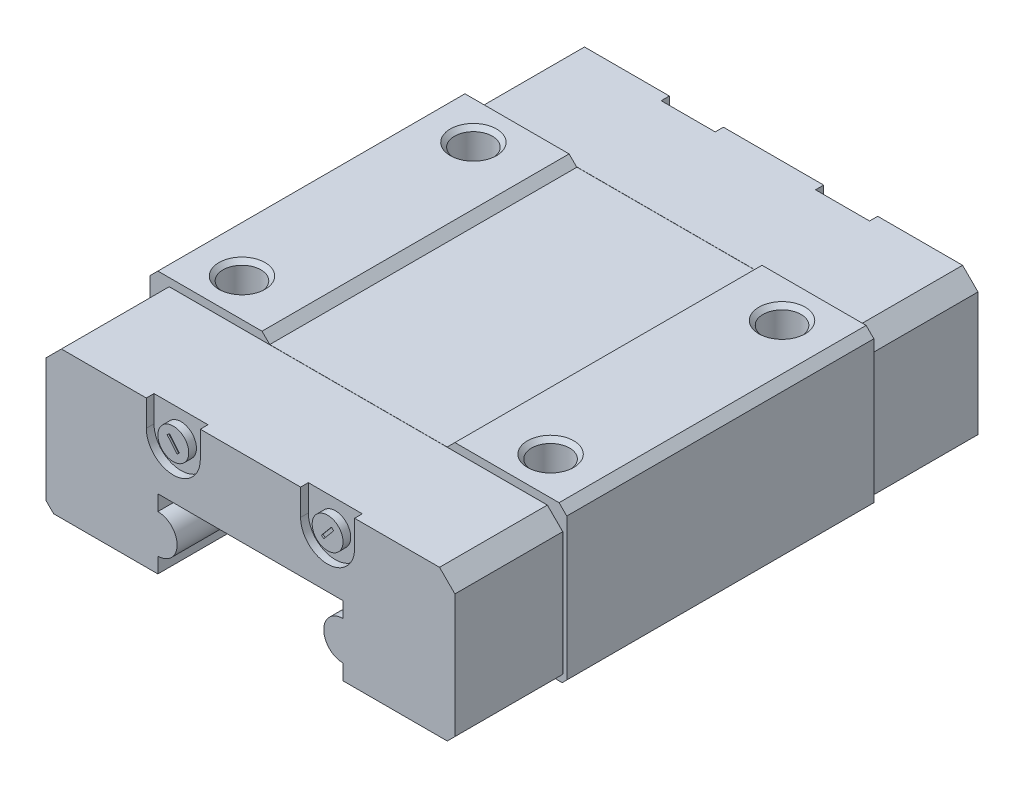
SolidWorks part; units mm, degrees
ref_plane "前视基准面" through (0, 0, 0) normal (0, 0, 1) x (1, 0, 0)
ref_plane "上视基准面" through (0, 0, 0) normal (0, 1, 0) x (1, 0, 0)
ref_plane "右视基准面" through (0, 0, 0) normal (1, 0, 0) x (0, 0, -1)
sketch "草图1" plane through (0, 0, 0) normal (0, 0, 1) x (1, 0, 0)
  line L0 (-13.5, 9.5) -> (-13.5, 0.297)
  line L1 (-13.5, 0.297) -> (-13.203, 0)
  line L2 (-13.203, 0) -> (-6, 0)
  line L3 (-6, 0) -> (-6, 1)
  line L4 (-6, 3.5) -> (-6, 4.5)
  line L5 (-6, 4.5) -> (6, 4.5)
  line L6 (6, 4.5) -> (6, 3.5)
  line L7 (6, 1) -> (6, 0)
  line L8 (6, 0) -> (13.203, 0)
  line L9 (13.203, 0) -> (13.5, 0.297)
  line L10 (13.5, 0.297) -> (13.5, 9.5)
  line L11 (13.5, 9.5) -> (13, 10)
  line L12 (13, 10) -> (6.25, 10)
  line L13 (6.25, 10) -> (5.75, 9.5)
  line L14 (5.75, 9.5) -> (-5.75, 9.5)
  line L15 (-5.75, 9.5) -> (-6.25, 10)
  line L16 (-6.25, 10) -> (-13, 10)
  line L17 (-13, 10) -> (-13.5, 9.5)
  arc A0 (-6, 1) -> (-6, 3.5) centre (-6, 2.25) ccw
  arc A1 (6, 3.5) -> (6, 1) centre (6, 2.25) ccw
extrude "凸台-拉伸1" add sketch "草图1" against normal blind 9.95 and the other way blind 9.95
ref_plane "基准面4" through (0, 0, 9.95) normal (0, 0, 1) x (1, 0, 0)
ref_plane "基准面5" through (0, 0, -9.95) normal (0, 0, 1) x (1, 0, 0)
sketch "草图2" plane through (0, 0, 9.95) normal (0, 0, 1) x (1, 0, 0)
  line L0 (-13.25, 8.503) -> (-13.25, 0.495)
  line L1 (-13.25, 0.495) -> (-12.755, 0)
  line L2 (-12.755, 0) -> (-6, 0)
  line L3 (-6, 0) -> (-6, 1)
  line L4 (-6, 3.5) -> (-6, 4.5)
  line L5 (-6, 4.5) -> (6, 4.5)
  line L6 (6, 4.5) -> (6, 3.5)
  line L7 (6, 1) -> (6, 0)
  line L8 (6, 0) -> (12.755, 0)
  line L9 (12.755, 0) -> (13.25, 0.495)
  line L10 (13.25, 0.495) -> (13.25, 8.503)
  line L11 (13.25, 8.503) -> (12.253, 9.5)
  line L12 (12.253, 9.5) -> (-12.253, 9.5)
  line L13 (-12.253, 9.5) -> (-13.25, 8.503)
  arc A0 (-6, 1) -> (-6, 3.5) centre (-6, 2.25) ccw
  arc A1 (6, 3.5) -> (6, 1) centre (6, 2.25) ccw
extrude "凸台-拉伸2" add sketch "草图2" along normal blind 7
sketch "草图3" plane through (0, 0, 9.95) normal (0, 0, 1) x (1, 0, 0)
  line L0 (-33.9, 33.9) -> (-33.9, -33.9)
  line L1 (-33.9, -33.9) -> (33.9, -33.9)
  line L2 (33.9, -33.9) -> (33.9, 33.9)
  line L3 (33.9, 33.9) -> (-33.9, 33.9)
  line L4 (-13.24, 8.493) -> (-13.24, 0.505)
  line L5 (-13.24, 0.505) -> (-12.745, 0.01)
  line L6 (-12.745, 0.01) -> (-6.01, 0.01)
  line L7 (-6.01, 0.01) -> (-6.01, 1.03)
  line L8 (-6.01, 3.49) -> (-6.01, 4.52)
  line L9 (-6.01, 4.52) -> (6.01, 4.52)
  line L10 (6.01, 4.52) -> (6.01, 3.49)
  line L11 (6.01, 1.03) -> (6.01, 0.01)
  line L12 (6.01, 0.01) -> (12.745, 0.01)
  line L13 (12.745, 0.01) -> (13.24, 0.505)
  line L14 (13.24, 0.505) -> (13.24, 8.493)
  line L15 (13.24, 8.493) -> (12.243, 9.49)
  line L16 (12.243, 9.49) -> (-12.243, 9.49)
  line L17 (-12.243, 9.49) -> (-13.24, 8.493)
  arc A0 (-6.01, 1.03) -> (-6.01, 3.49) centre (-6.01, 2.26) ccw
  arc A1 (6.01, 3.49) -> (6.01, 1.03) centre (6.01, 2.26) ccw
extrude "切除-拉伸1" cut sketch "草图3" along normal blind 0.02
sketch "草图4" plane through (0, 0, -9.95) normal (0, 0, 1) x (1, 0, 0)
  line L0 (-13.25, 8.503) -> (-13.25, 0.495)
  line L1 (-13.25, 0.495) -> (-12.755, 0)
  line L2 (-12.755, 0) -> (-6, 0)
  line L3 (-6, 0) -> (-6, 1)
  line L4 (-6, 3.5) -> (-6, 4.5)
  line L5 (-6, 4.5) -> (6, 4.5)
  line L6 (6, 4.5) -> (6, 3.5)
  line L7 (6, 1) -> (6, 0)
  line L8 (6, 0) -> (12.755, 0)
  line L9 (12.755, 0) -> (13.25, 0.495)
  line L10 (13.25, 0.495) -> (13.25, 8.503)
  line L11 (13.25, 8.503) -> (12.253, 9.5)
  line L12 (12.253, 9.5) -> (-12.253, 9.5)
  line L13 (-12.253, 9.5) -> (-13.25, 8.503)
  arc A0 (-6, 1) -> (-6, 3.5) centre (-6, 2.25) ccw
  arc A1 (6, 3.5) -> (6, 1) centre (6, 2.25) ccw
extrude "凸台-拉伸3" add sketch "草图4" against normal blind 7
sketch "草图5" plane through (0, 0, -9.95) normal (0, 0, 1) x (1, 0, 0)
  line L0 (-33.9, 33.9) -> (-33.9, -33.9)
  line L1 (-33.9, -33.9) -> (33.9, -33.9)
  line L2 (33.9, -33.9) -> (33.9, 33.9)
  line L3 (33.9, 33.9) -> (-33.9, 33.9)
  line L4 (-13.24, 8.493) -> (-13.24, 0.505)
  line L5 (-13.24, 0.505) -> (-12.745, 0.01)
  line L6 (-12.745, 0.01) -> (-6.01, 0.01)
  line L7 (-6.01, 0.01) -> (-6.01, 1.03)
  line L8 (-6.01, 3.49) -> (-6.01, 4.52)
  line L9 (-6.01, 4.52) -> (6.01, 4.52)
  line L10 (6.01, 4.52) -> (6.01, 3.49)
  line L11 (6.01, 1.03) -> (6.01, 0.01)
  line L12 (6.01, 0.01) -> (12.745, 0.01)
  line L13 (12.745, 0.01) -> (13.24, 0.505)
  line L14 (13.24, 0.505) -> (13.24, 8.493)
  line L15 (13.24, 8.493) -> (12.243, 9.49)
  line L16 (12.243, 9.49) -> (-12.243, 9.49)
  line L17 (-12.243, 9.49) -> (-13.24, 8.493)
  arc A0 (-6.01, 1.03) -> (-6.01, 3.49) centre (-6.01, 2.26) ccw
  arc A1 (6.01, 3.49) -> (6.01, 1.03) centre (6.01, 2.26) ccw
extrude "切除-拉伸2" cut sketch "草图5" against normal blind 0.02
ref_plane "基准面6" through (0, 0, -16.95) normal (0, 0, 1) x (1, 0, 0)
sketch "草图6" plane through (0, 0, -16.95) normal (0, 0, 1) x (1, 0, 0)
  line L0 (-6.75, 26) -> (-6.75, 7.8)
  line L1 (-3.25, 7.8) -> (-3.25, 24.825)
  line L2 (-3.25, 24.825) -> (3.25, 24.825)
  line L3 (3.25, 24.825) -> (3.25, 7.8)
  line L4 (6.75, 7.8) -> (6.75, 26)
  line L5 (6.75, 26) -> (-6.75, 26)
  arc A0 (-6.75, 7.8) -> (-3.25, 7.8) centre (-5, 7.8) ccw
  arc A1 (3.25, 7.8) -> (6.75, 7.8) centre (5, 7.8) ccw
extrude "切除-拉伸3" cut sketch "草图6" along normal blind 0.53
sketch "草图7" plane through (0, 0, -16.95) normal (0, 0, 1) x (1, 0, 0)
  circle A0 centre (-5, 7.8) radius 1
extrude "凸台-拉伸4" add sketch "草图7" along normal blind 1
sketch "草图8" plane through (0, 0, -16.95) normal (0, 0, 1) x (1, 0, 0)
  circle A0 centre (5, 7.8) radius 1
extrude "凸台-拉伸5" add sketch "草图8" along normal blind 1
ref_plane "基准面7" through (0, 0, 16.95) normal (0, 0, 1) x (1, 0, 0)
sketch "草图9" plane through (0, 0, 16.95) normal (0, 0, 1) x (1, 0, 0)
  line L0 (-6.75, 26) -> (-6.75, 7.8)
  line L1 (-3.25, 7.8) -> (-3.25, 24.825)
  line L2 (-3.25, 24.825) -> (3.25, 24.825)
  line L3 (3.25, 24.825) -> (3.25, 7.8)
  line L4 (6.75, 7.8) -> (6.75, 26)
  line L5 (6.75, 26) -> (-6.75, 26)
  arc A0 (-6.75, 7.8) -> (-3.25, 7.8) centre (-5, 7.8) ccw
  arc A1 (3.25, 7.8) -> (6.75, 7.8) centre (5, 7.8) ccw
extrude "切除-拉伸4" cut sketch "草图9" against normal blind 0.5
sketch "草图10" plane through (0, 0, 16.95) normal (0, 0, 1) x (1, 0, 0)
  circle A0 centre (-5, 7.8) radius 1
extrude "凸台-拉伸6" add sketch "草图10" against normal blind 1
sketch "草图11" plane through (0, 0, 16.95) normal (0, 0, 1) x (1, 0, 0)
  circle A0 centre (5, 7.8) radius 1
extrude "凸台-拉伸7" add sketch "草图11" against normal blind 1
ref_plane "基准面8" through (0, 10, 0) normal (0, 1, 0) x (1, 0, 0)
ref_plane "基准面9" through (10, 0, 0) normal (1, 0, 0) x (0, 0, -1)
sketch "草图12" plane through (10, 0, 0) normal (1, 0, 0) x (0, 0, -1)
  line L0 (-7.5, 10) -> (-6, 10)
  line L1 (-6, 10) -> (-6.2705, 9.7295)
  line L2 (-6.2705, 9.7295) -> (-6.2705, 5.4599)
  line L3 (-6.2705, 5.4599) -> (-7.5, 4.75)
  line L4 (-7.5, 4.75) -> (-7.5, 10)
  line L5 (-7.5, 4.75) -> (-7.5, 10) construction
revolve "切除-旋转1" cut sketch "草图12" angle 360 about L5 reverse direction yes
cosmetic thread "装饰螺纹线1" parameters "D1"=3.5, "D2"=3
sketch "草图13" plane through (0, 0, 0) normal (0, 1, 0) x (1, 0, 0)
  line L0 (10, -7.5) -> (10, 992.5)
  line L1 (10, -7.5) -> (-990, -7.5)
pattern_linear "阵列(线性)1" count 2 spacing 15 along (0, 0, -1) count 2 spacing 20 along (-1, 0, 0) of "切除-旋转1"
sketch "草图14" plane through (0, 0, 16.95) normal (0, 0, 1) x (1, 0, 0)
  line L0 (4.602, 7.4813) -> (4.7552, 7.3527)
  line L1 (4.7552, 7.3527) -> (5.398, 8.1187)
  line L2 (5.398, 8.1187) -> (5.2448, 8.2473)
  line L3 (5.2448, 8.2473) -> (4.602, 7.4813)
extrude "切除-拉伸5" cut sketch "草图14" against normal blind 0.1
sketch "草图15" plane through (0, 0, 16.95) normal (0, 0, 1) x (1, 0, 0)
  line L0 (-5.398, 8.1187) -> (-4.7552, 7.3527)
  line L1 (-4.7552, 7.3527) -> (-4.602, 7.4813)
  line L2 (-4.602, 7.4813) -> (-5.2448, 8.2473)
  line L3 (-5.2448, 8.2473) -> (-5.398, 8.1187)
extrude "切除-拉伸6" cut sketch "草图15" against normal blind 0.1
sketch "草图16" plane through (0, 0, -16.95) normal (0, 0, 1) x (1, 0, 0)
  line L0 (4.602, 7.4813) -> (4.7552, 7.3527)
  line L1 (4.7552, 7.3527) -> (5.398, 8.1187)
  line L2 (5.398, 8.1187) -> (5.2448, 8.2473)
  line L3 (5.2448, 8.2473) -> (4.602, 7.4813)
extrude "切除-拉伸7" cut sketch "草图16" along normal blind 0.1
sketch "草图17" plane through (0, 0, -16.95) normal (0, 0, 1) x (1, 0, 0)
  line L0 (-5.398, 8.1187) -> (-4.7552, 7.3527)
  line L1 (-4.7552, 7.3527) -> (-4.602, 7.4813)
  line L2 (-4.602, 7.4813) -> (-5.2448, 8.2473)
  line L3 (-5.2448, 8.2473) -> (-5.398, 8.1187)
extrude "切除-拉伸8" cut sketch "草图17" along normal blind 0.1
ref_plane "基准面10" through (0, 4.5, 0) normal (0, 1, 0) x (1, 0, 0)
ref_plane "基准面11" through (0, 0, 0) normal (0, 0, 1) x (1, 0, 0)
ref_plane "to_rail XY" through (0, 0, 0) normal (0, 0, 1) x (1, 0, 0)
ref_plane "to_rail XZ" through (0, 4.5, 0) normal (0, -1, 0) x (-1, 0, 0)
ref_plane "to_rail YZ" through (0, 0, 0) normal (1, 0, 0) x (0, 0, -1)
ref_axis "to_rail X" through (-80.9, 4.5, 0) along (1, 0, 0)
ref_axis "to_rail Y" through (0, -50, 0) along (0, 1, 0)
ref_axis "to_rail Z" through (0, 4.5, 80.9) along (0, 0, -1)
sketch3d "to_rail"
  point P0 (0, 4.5, 0)
